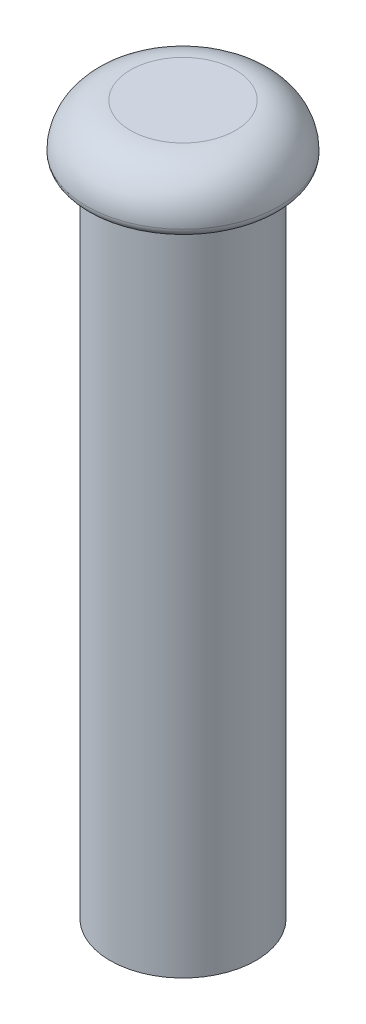
SolidWorks part; units mm, degrees
material "Stop 1060"
ref_plane "Płaszczyzna przednia" through (0, 0, 0) normal (0, 0, 1) x (1, 0, 0)
ref_plane "Płaszczyzna górna" through (0, 0, 0) normal (0, 1, 0) x (1, 0, 0)
ref_plane "Płaszczyzna prawa" through (0, 0, 0) normal (1, 0, 0) x (0, 0, -1)
sketch "Szkic1" plane through (0, 0, 0) normal (0, 1, 0) x (1, 0, 0)
  circle A0 centre (0, 0) radius 25
  dimension "D1" = 50
extrude "Dodanie-wyciągnięcie1" add sketch "Szkic1" along normal blind 225
sketch "Szkic2" plane through (0, 225, 0) normal (0, 1, 0) x (1, 0, 0)
  circle A0 centre (0, 0) radius 33
  dimension "D1" = 66
extrude "Dodanie-wyciągnięcie2" add sketch "Szkic2" along normal blind 18
fillet "Zaokrąglenie1" radius 15 1 edges at (0, 243, 33)
fillet "Zaokrąglenie2" radius 3 1 edges at (0, 225, 33)
